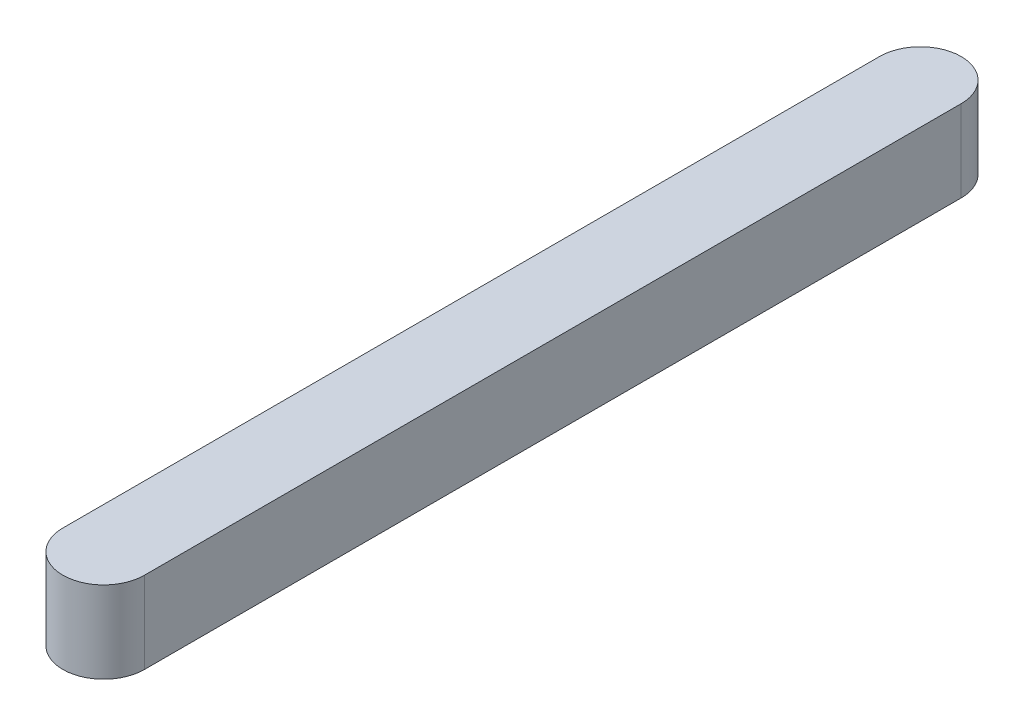
SolidWorks part; units mm, degrees
ref_plane "Front Plane" through (0, 0, 0) normal (0, 0, 1) x (1, 0, 0)
ref_plane "Top Plane" through (0, 0, 0) normal (0, 1, 0) x (1, 0, 0)
ref_plane "Right Plane" through (0, 0, 0) normal (1, 0, 0) x (0, 0, -1)
ref_axis "X AXIS" through (-88.99, 0, 0) along (1, 0, 0)
ref_axis "Y AXIS" through (0, 55, 0) along (0, -1, 0)
ref_axis "Z AXIS" through (0, 0, -88.99) along (0, 0, 1)
sketch "Sketch1" plane through (0, 0, 0) normal (1, 0, 0) x (0, 0, -1)
  line L1 (0, 0) -> (34.925, 0)
  line L2 (0, 0) -> (0, 3.175)
  line L3 (0, 3.175) -> (34.925, 3.175)
  line L4 (34.925, 0) -> (34.925, 3.175)
  dimension "D1" = 34.925
  dimension "D2" = 3.175
extrude "Boss-Extrude1" add sketch "Sketch1" along normal blind 3.175
fillet "Fillet1" 2 edges at (3.175, 1.5875, 0) (0, 1.5875, 0) type full round first side face at (3.175, 1.5875, -17.4625) second side face at (0, 1.5875, -17.4625) middle face at (1.5875, 1.5875, 0)
fillet "Fillet2" 2 edges at (3.175, 1.5875, -34.925) (0, 1.5875, -34.925) type full round first side face at (3.175, 1.5875, -18.2562) second side face at (0, 1.5875, -18.2562) middle face at (1.5875, 1.5875, -34.925)
